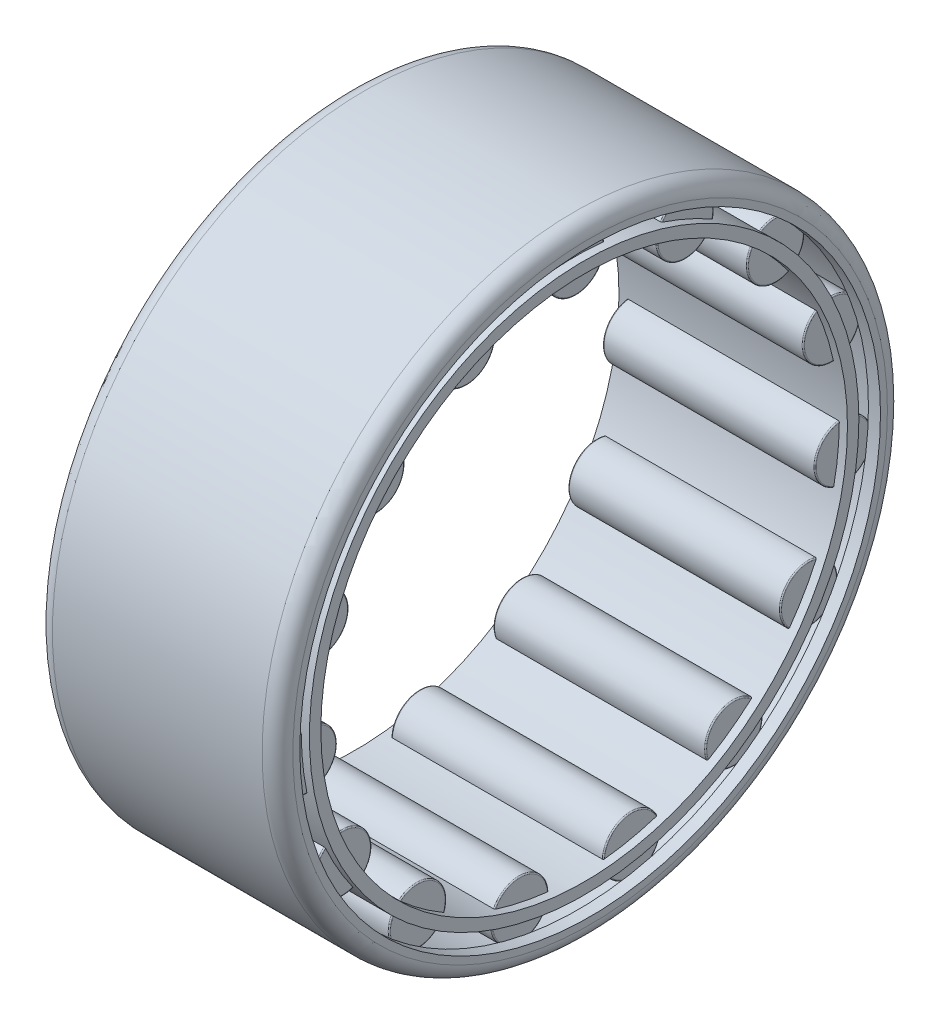
SolidWorks part; units mm, degrees
ref_plane "Plane1" through (0, 0, 0) normal (0, 0, 1) x (1, 0, 0)
ref_plane "Plane2" through (0, 0, 0) normal (0, 1, 0) x (1, 0, 0)
ref_plane "Plane3" through (0, 0, 0) normal (1, 0, 0) x (0, 0, -1)
sketch "Clipboard" plane through (0, 0, 0) normal (0, 0, 1) x (1, 0, 0)
  line L0 (-10, 0) -> (10, 0) construction
  line L1 (41.1529, 1.4371) -> (62.7517, -4.3503)
  line L2 (41.1529, 1.4371) -> (75.4583, 10.6292)
  line L3 (41.1529, 1.4371) -> (62.7517, -4.3503)
  line L4 (41.1529, 1.4371) -> (-22.3471, -0.7804)
  dimension "BallCLRad" = 35.5155
  dimension "Bore" = 63.5
sketch "InnRacSke" plane through (0, 0, 0) normal (0, 0, 1) x (1, 0, 0)
  line L0 (-14.2875, 38.3286) -> (-15.875, 38.3286)
  line L1 (-15.875, 38.3286) -> (-15.875, 39.243)
  line L2 (-13.843, 41.275) -> (13.843, 41.275)
  line L4 (15.875, 39.243) -> (15.875, 38.3286)
  line L5 (15.875, 38.3286) -> (14.2875, 38.3286)
  line L6 (14.2875, 38.3286) -> (14.2875, 39.2811)
  line L7 (14.2875, 39.2811) -> (-14.2875, 39.2811)
  line L8 (-14.2875, 39.2811) -> (-14.2875, 38.3286)
  line L9 (-31.75, 0) -> (31.75, 0) construction
  arc A0 (-15.875, 39.243) -> (-13.843, 41.275) centre (-13.843, 39.243) cw
  arc A2 (13.843, 41.275) -> (15.875, 39.243) centre (13.843, 39.243) cw
  dimension "D1" = 78.5622
revolve "Race" add sketch "InnRacSke" angle 360 about L9 reverse direction yes
sketch "RolDetSke" plane through (0, 0, 0) normal (0, 0, 1) x (1, 0, 0)
  line L0 (-14.0018, 39.131) -> (-14.0017, 35.5155)
  line L1 (-14.0017, 35.5155) -> (14.0017, 35.5155)
  line L2 (14.0017, 35.5155) -> (14.0018, 39.131)
  line L3 (13.8511, 39.2816) -> (-13.8511, 39.2816)
  line L4 (-28.575, 35.5155) -> (28.575, 35.5155) construction
  arc A0 (14.0018, 39.131) -> (13.8511, 39.2816) centre (13.8511, 39.131) ccw
  arc A1 (-13.8511, 39.2816) -> (-14.0018, 39.131) centre (-13.8511, 39.131) ccw
  dimension "Roller_length" = 28.0035
  dimension "Roller_diameter" = 7.5321
revolve "RollerDetailed" add sketch "RolDetSke" angle 360 about L4 reverse direction yes
ref_axis "Axis1" through (-50, 0, 0) along (1, 0, 0)
sketch "CagSpiSke" plane through (0, 0, 0) normal (0, 0, 1) x (1, 0, 0)
  line L0 (15.0812, 34.7623) -> (15.0812, 36.2688)
  line L1 (15.0812, 36.2688) -> (-15.0813, 36.2688)
  line L2 (-15.0813, 36.2688) -> (-15.0813, 34.7623)
  line L3 (-15.0813, 34.7623) -> (15.0812, 34.7623)
  line L4 (-31.75, 0) -> (31.75, 0) construction
  dimension "D2" = 69.5247
  dimension "halfWidth" = 15.0813
revolve "CageSpine" add sketch "CagSpiSke" angle 360 about L4 reverse direction yes
pattern_circular "RollersDetailed" count 15 every 24 about axis through (-50, 0, 0) along (1, 0, 0) of "RollerDetailed"
sketch "RolSimSke" plane through (0, 0, 0) normal (0, 0, 1) x (1, 0, 0)
  line L0 (-25.4, 0) -> (25.4, 0) construction
  line L2 (-13.8511, 39.2821) -> (13.8511, 39.2821)
  line L3 (-14.0018, 39.1315) -> (-14.0018, 31.9006)
  line L4 (-13.8511, 31.75) -> (13.8511, 31.75)
  line L5 (14.0017, 39.1315) -> (14.0017, 31.9006)
  arc A0 (-14.0018, 31.9006) -> (-13.8511, 31.75) centre (-13.8511, 31.9006) ccw
  arc A1 (-13.8511, 39.2821) -> (-14.0018, 39.1315) centre (-13.8511, 39.1315) ccw
  arc A2 (14.0017, 39.1315) -> (13.8511, 39.2821) centre (13.8511, 39.1315) ccw
  arc A3 (13.8511, 31.75) -> (14.0017, 31.9006) centre (13.8511, 31.9006) ccw
  point P10 (-14.0018, 31.75)
  point P15 (14.0017, 39.2821)
  point P18 (14.0017, 31.75)
  dimension "Bore" = 63.5
  dimension "D1" = 0.1506
  dimension "Roller_length" = 28.0035
  dimension "Roller_diameter" = 7.5321
  dimension "halfWidth" = 14.0017
revolve "RollersSimplified" [suppressed] add sketch "RolSimSke" angle 360 about L0
equation "\"BallCLRad@Clipboard\" =  ( \"D1@InnRacSke\" + \"Bore@Clipboard\" )  / 4"
equation "\"RollerCLRad@RolDetSke\" = \"BallCLRad@Clipboard\""
equation "\"halfCyl@InnRacSke\" = \"Cyl_Len@InnRacSke\" / 2"
equation "\"Roller_diameter@RolDetSke\" =  ( \"D1@InnRacSke\" - \"Bore@Clipboard\" )  / 2 + .001"
equation "\"Roller_radius@RolDetSke\" = \"Roller_diameter@RolDetSke\" / 50"
equation "\"Roller_length@RolDetSke\" = \"Cyl_Len@InnRacSke\" * .98"
equation "\"halfLength@RolDetSke\" = \"Roller_length@RolDetSke\" / 2"
equation "\"Cage_width@CagSpiSke\" =  ( \"Cyl_Len@InnRacSke\" + \"Width@InnRacSke\" )  / 2"
equation "\"halfWidth@CagSpiSke\" = \"Cage_width@CagSpiSke\" / 2"
equation "\"Cage_thickness@CagSpiSke\"  = \"Roller_diameter@RolDetSke\" / 5"
equation "\"D2@CagSpiSke\" =  \"RollerCLRad@RolDetSke\" * 2 - \"Cage_thickness@CagSpiSke\""
equation "\"Roller_length@RolSimSke\" = \"Cyl_Len@InnRacSke\" * .98"
equation "\"halfWidth@RolSimSke\" = \"Roller_length@RolSimSke\" / 2"
equation "\"D1@RolSimSke\" = \"Roller_radius@RolDetSke\""
equation "\"Roller_diameter@RolSimSke\" =  ( \"D1@InnRacSke\" - \"Bore@Clipboard\" )  / 2 + .001"
equation "\"Max_count@Clipboard\" = int( 3.14159265 / atn(( \"Roller_diameter@RolDetSke\" / 2) / sqr( \"RollerCLRad@RolDetSke\"  *  \"RollerCLRad@RolDetSke\" - ( \"Roller_diameter@RolDetSke\" / 2) *  ( \"Roller_diameter@RolDetSke\" / 2))))"
equation "\"Max_count@Clipboard\" = ((sgn( \"Max_count@Clipboard\" - \"Count@Clipboard\" )-1)*( \"Max_count@Clipboard\" - \"Count@Clipboard\" ))/-2+ \"Count@Clipboard\""
equation "\"Count@RollersDetailed\" = int( \"Show_count@Clipboard\" ) "
equation "\"Count@RollersDetailed\" = ((sgn( \"Count@RollersDetailed\" - \"Max_count@Clipboard\" )-1)*( \"Count@RollersDetailed\" - \"Max_count@Clipboard\" ))/-2+ \"Max_count@Clipboard\""
equation "\"Count@RollersDetailed\" = ((sgn( \"Count@RollersDetailed\" - \"Min_count@Clipboard\" )+1)*( \"Count@RollersDetailed\" - \"Min_count@Clipboard\"))/2 +\"Min_count@Clipboard\""
equation "\"Angle@RollersDetailed\" = 360.0 / \"Max_count@Clipboard\""
equation "\"Angle@CageSpine\" =  \"Angle@RollersDetailed\" * ( \"Count@RollersDetailed\" -1 + int( \"Count@RollersDetailed\" / \"Max_count@Clipboard\" ) )  + 0.001 -  int( \"Count@RollersDetailed\" / \"Max_count@Clipboard\" ) * 0.001"
equation "\"Angle@CageSpine\" =  \"Angle@CageSpine\" * int( \"Min_count@Clipboard\" / 2) + int(1 / \"Min_count@Clipboard\")  * 0.001"
equation "\"Bore@RolSimSke\" = \"Bore@Clipboard\""
